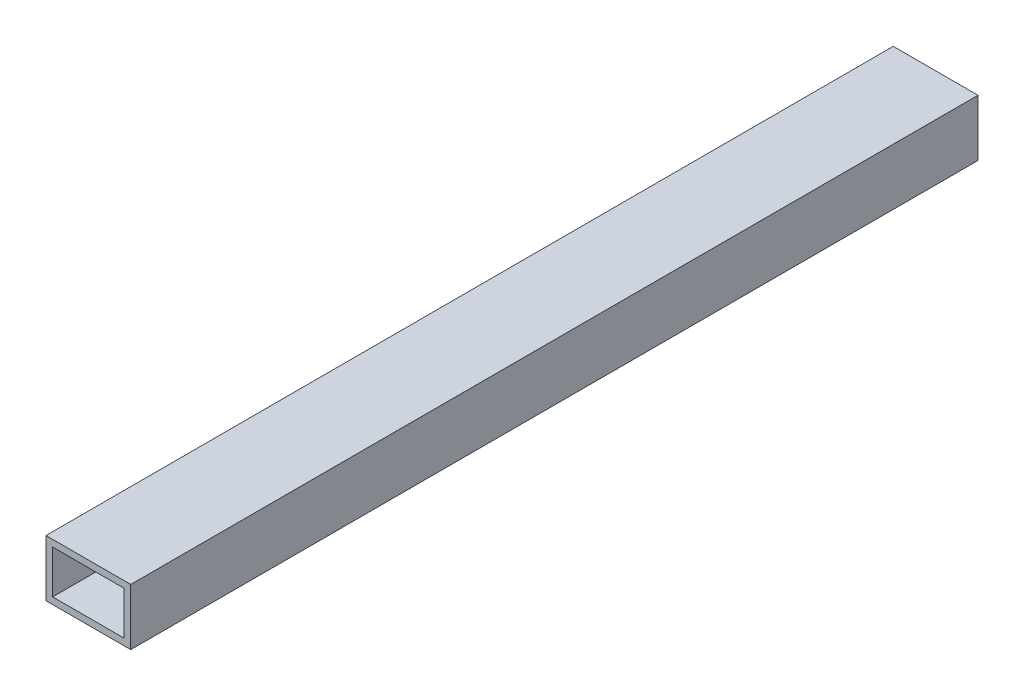
SolidWorks part; units mm, degrees
ref_plane "Front Plane" through (0, 0, 0) normal (0, 0, 1) x (1, 0, 0)
ref_plane "Top Plane" through (0, 0, 0) normal (0, 1, 0) x (1, 0, 0)
ref_plane "Right Plane" through (0, 0, 0) normal (1, 0, 0) x (0, 0, -1)
sketch "Sketch2" plane through (0, 0, 0) normal (0, 0, 1) x (1, 0, 0)
  line L1 (-38.1, -25.4) -> (38.1, -25.4)
  line L2 (-38.1, -25.4) -> (-38.1, 25.4)
  line L3 (-38.1, 25.4) -> (38.1, 25.4)
  line L4 (38.1, -25.4) -> (38.1, 25.4)
  line L5 (-38.1, -25.4) -> (38.1, 25.4) construction
  line L6 (-38.1, 25.4) -> (38.1, -25.4) construction
  line L7 (-32.1, -19.4) -> (32.1, -19.4)
  line L8 (-32.1, -19.4) -> (-32.1, 19.4)
  line L9 (-32.1, 19.4) -> (32.1, 19.4)
  line L10 (32.1, -19.4) -> (32.1, 19.4)
  line L11 (-32.1, -19.4) -> (32.1, 19.4) construction
  line L12 (-32.1, 19.4) -> (32.1, -19.4) construction
  point P0 (0, 0)
  point P6 (0, 0)
  dimension "D1" = 76.2
  dimension "D2" = 50.8
  dimension "D3" = 6
  dimension "D4" = 6
extrude "Boss-Extrude1" add sketch "Sketch2" along normal blind 762
